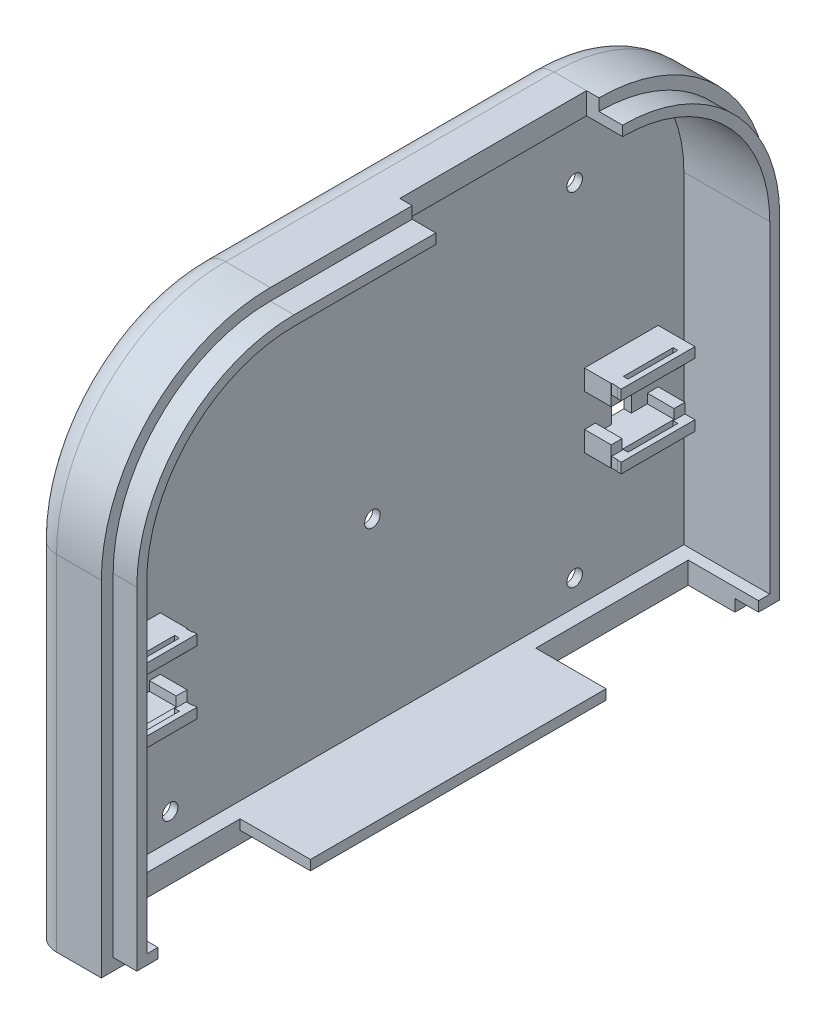
SolidWorks part; units mm, degrees
ref_plane "Front Plane" through (0, 0, 0) normal (0, 0, 1) x (1, 0, 0)
ref_plane "Top Plane" through (0, 0, 0) normal (0, 1, 0) x (1, 0, 0)
ref_plane "Right Plane" through (0, 0, 0) normal (1, 0, 0) x (0, 0, -1)
sketch "Sketch1" plane through (0, 0, 0) normal (1, 0, 0) x (0, 0, -1)
  line L0 (-52.8, 94.65) -> (52.8, 94.65)
  line L1 (-107.1, 40.35) -> (-107.1, -40.35)
  line L2 (-70, -70.35) -> (70, -70.35)
  line L3 (107.1, 40.35) -> (107.1, -40.35)
  line L4 (107.1, 0) -> (-107.1, 0) construction
  line L5 (0, 94.65) -> (0, -70.35) construction
  line L11 (107.1, -40.35) -> (107.1, -70.35)
  line L12 (107.1, -70.35) -> (70, -70.35)
  line L13 (-83.2, -1.7) -> (-76.8, -1.7)
  line L14 (-83.2, -1.7) -> (-83.2, -18.3)
  line L15 (-83.2, -18.3) -> (-76.8, -18.3)
  line L16 (-76.8, -1.7) -> (-76.8, -18.3)
  line L17 (-83.2, -1.7) -> (-76.8, -18.3) construction
  line L18 (-83.2, -18.3) -> (-76.8, -1.7) construction
  line L19 (76.8, -1.7) -> (83.2, -1.7)
  line L20 (76.8, -1.7) -> (76.8, -18.3)
  line L21 (76.8, -18.3) -> (83.2, -18.3)
  line L22 (83.2, -1.7) -> (83.2, -18.3)
  line L23 (76.8, -1.7) -> (83.2, -18.3) construction
  line L24 (76.8, -18.3) -> (83.2, -1.7) construction
  line L25 (80, -10) -> (-80, -10) construction
  line L27 (-107.1, -40.35) -> (-107.1, -70.35)
  line L28 (-107.1, -70.35) -> (-70, -70.35)
  arc A0 (52.8, 94.65) -> (107.1, 40.35) centre (52.8, 40.35) cw
  arc A1 (-52.8, 94.65) -> (-107.1, 40.35) centre (-52.8, 40.35) ccw
  point P16 (0, 0)
  point P17 (-80, -10)
  point P19 (80, 5)
  point P20 (0, -11.7555)
  point P32 (80, -10)
  point P39 (-80, -10)
  point P40 (0, -10)
  dimension "D4" = 54.3
  dimension "D2" = 165
  dimension "D3" = 214.2
  dimension "D5" = 140
  dimension "D6" = 30
  dimension "D7" = 160
  dimension "D8" = 6.4
  dimension "D9" = 16.6
  dimension "D10" = 6.4
  dimension "D11" = 16.6
  dimension "D12" = 10
extrude "Boss-Extrude1" add sketch "Sketch1" along normal blind 2.4 contours L2 L3 A0 L0 A1 L1 L19 L22 L21 L20 L13 L16 L15 L14 region at (0, 9.6593, 0)
sketch "Sketch9" plane through (2.4, 0, 0) normal (1, 0, 0) x (0, 0, -1)
  line L17 (52.8, 94.65) -> (-52.8, 94.65)
  line L31 (52.8, 94.65) -> (-52.8, 94.65)
  line L32 (-107.1, 40.35) -> (-107.1, -70.35)
  line L33 (-107.1, 40.35) -> (-107.1, -70.35)
  line L34 (-107.1, -70.35) -> (107.1, -70.35)
  line L39 (107.1, -70.35) -> (107.1, 40.35)
  line L43 (107.1, -70.35) -> (107.1, 40.35)
  line L45 (-107.1, -70.35) -> (107.1, -70.35)
  arc A15 (-52.8, 94.65) -> (-107.1, 40.35) centre (-52.8, 40.35) ccw
  arc A16 (-52.8, 94.65) -> (-107.1, 40.35) centre (-52.8, 40.35) ccw
  arc A17 (107.1, 40.35) -> (52.8, 94.65) centre (52.8, 40.35) ccw
  arc A18 (107.1, 40.35) -> (52.8, 94.65) centre (52.8, 40.35) ccw
  dimension "D1" = 0
sketch "Sketch10" plane through (2.4, 0, 0) normal (1, 0, 0) x (0, 0, -1)
  line L0 (65, -55.05) -> (0, -55.05) construction
  line L1 (-65, -55.05) -> (65, -55.05) construction
  line L2 (-65, -55.05) -> (-65, 54.95) construction
  line L3 (-65, 54.95) -> (65, 54.95) construction
  line L4 (65, -55.05) -> (65, 54.95) construction
  line L5 (-65, -55.05) -> (65, 54.95) construction
  line L6 (-65, 54.95) -> (65, -55.05) construction
  line L7 (0, -55.05) -> (-65, -55.05) construction
  line L8 (-107.1, -70.35) -> (107.1, -70.35) construction
  line L9 (0, -0.05) -> (0, 0) construction
  line L10 (0, -0.05) -> (0, -6.1) construction
  circle A4 centre (65, 54.95) radius 2.5
  circle A5 centre (65, -55.05) radius 2.5
  circle A6 centre (-65, -55.05) radius 2.5
  circle A7 centre (-65, 54.95) radius 2.5
  circle A11 centre (0, -6.1) radius 2.5
  point P0 (0, -0.05)
  point P11 (0, -55.05)
  point P12 (32.5, -55.05)
  point P14 (-32.5, -55.05)
  dimension "D3" = 5
  dimension "D4" = 15.3
  dimension "D1" = 130
  dimension "D2" = 110
  dimension "D5" = 6.05
extrude "Cut-Extrude1" cut sketch "Sketch10" against normal blind 100 and the other way blind 1000
sketch "Sketch12" plane through (2.4, 0, 0) normal (1, 0, 0) x (0, 0, -1)
  line L5 (-88.35, -18.3) -> (-88.35, -15.3)
  line L6 (-88.35, -18.3) -> (-88.35, -1.7) construction
  line L22 (71.65, -18.3) -> (71.65, -15.3)
  line L23 (71.65, -18.3) -> (71.65, -1.7) construction
  line L24 (71.65, -18.3) -> (88.35, -18.3) construction
  line L25 (88.35, -18.3) -> (88.35, -1.7) construction
  line L26 (71.65, -1.7) -> (88.35, -1.7) construction
  line L27 (71.65, -18.3) -> (88.35, -1.7) construction
  line L28 (88.35, -18.3) -> (71.65, -1.7) construction
  line L29 (71.65, -1.7) -> (71.65, -4.7)
  line L30 (88.35, -18.3) -> (88.35, -15.3)
  line L31 (88.35, -1.7) -> (88.35, -4.7)
  line L32 (71.65, -1.7) -> (88.35, -1.7)
  line L33 (88.35, -18.3) -> (71.65, -18.3)
  line L34 (88.35, -15.3) -> (91.85, -15.3)
  line L35 (71.65, -15.3) -> (68.15, -15.3)
  line L36 (68.15, -15.3) -> (68.15, -21.8)
  line L37 (68.15, -21.8) -> (91.85, -21.8)
  line L38 (91.85, -21.8) -> (91.85, -15.3)
  line L39 (71.65, -4.7) -> (68.15, -4.7)
  line L40 (68.15, -4.7) -> (68.15, 1.8)
  line L41 (68.15, 1.8) -> (91.85, 1.8)
  line L42 (91.85, 1.8) -> (91.85, -4.7)
  line L43 (91.85, -4.7) -> (88.35, -4.7)
  line L44 (83.2, -18.3) -> (76.8, -1.7) construction
  line L45 (83.2, -1.7) -> (76.8, -18.3) construction
  line L46 (-88.35, -18.3) -> (-71.65, -18.3) construction
  line L47 (-71.65, -18.3) -> (-71.65, -1.7) construction
  line L48 (-88.35, -1.7) -> (-71.65, -1.7) construction
  line L49 (-88.35, -18.3) -> (-71.65, -1.7) construction
  line L50 (-71.65, -18.3) -> (-88.35, -1.7) construction
  line L51 (-88.35, -1.7) -> (-88.35, -4.7)
  line L52 (-71.65, -18.3) -> (-71.65, -15.3)
  line L53 (-71.65, -1.7) -> (-71.65, -4.7)
  line L54 (-88.35, -1.7) -> (-71.65, -1.7)
  line L55 (-71.65, -18.3) -> (-88.35, -18.3)
  line L56 (-71.65, -15.3) -> (-68.15, -15.3)
  line L57 (-88.35, -15.3) -> (-91.85, -15.3)
  line L58 (-91.85, -15.3) -> (-91.85, -21.8)
  line L59 (-91.85, -21.8) -> (-68.15, -21.8)
  line L60 (-68.15, -21.8) -> (-68.15, -15.3)
  line L61 (-88.35, -4.7) -> (-91.85, -4.7)
  line L62 (-91.85, -4.7) -> (-91.85, 1.8)
  line L63 (-91.85, 1.8) -> (-68.15, 1.8)
  line L64 (-68.15, 1.8) -> (-68.15, -4.7)
  line L65 (-68.15, -4.7) -> (-71.65, -4.7)
  line L66 (-76.8, -18.3) -> (-83.2, -1.7) construction
  line L67 (-83.2, -18.3) -> (-76.8, -1.7) construction
  point P3 (-0.1438, 64.1533)
  point P4 (-80, -10)
  point P19 (80, -10)
  point P21 (-80, -10)
  point P30 (380.6447, 32.9453)
  point P31 (130.7088, -20.4974)
  point P32 (80, -10)
  point P49 (169.9078, -49.5925)
  dimension "D3" = 16.7
  dimension "D4" = 16.6
  dimension "D5" = 10.6
  dimension "D6" = 3.5
  dimension "D7" = 3.5
  dimension "D8" = 3.5
  dimension "D9" = 3.5
  dimension "D10" = 4.9497
  dimension "D11" = 16.7
  dimension "D12" = 16.6
  dimension "D13" = 10.6
  dimension "D14" = 3.5
  dimension "D15" = 3.5
  dimension "D16" = 3.5
  dimension "D17" = 3.5
  dimension "D18" = 4.9497
  dimension "D19" = 4.9497
  dimension "D20" = 7.3824
  dimension "D21" = 23.5468
  dimension "D22" = 24.088
  dimension "D23" = 4.9497
  dimension "D24" = 7.3824
  dimension "D25" = 23.5468
  dimension "D26" = 24.088
extrude "Boss-Extrude2" add sketch "Sketch12" along normal blind 8.6
sketch "Sketch14" plane through (11, 0, 0) normal (1, 0, 0) x (0, 0, -1)
  line L0 (-91.85, 1.8) -> (-91.85, -4.7) construction
  line L1 (-91.85, 1.8) -> (-68.15, 1.8)
  line L2 (-91.85, 1.8) -> (-91.85, -1.45)
  line L3 (-91.85, -1.45) -> (-68.15, -1.45)
  line L4 (-68.15, 1.8) -> (-68.15, -1.45)
  line L5 (-68.15, 1.8) -> (-91.85, 1.8) construction
  line L6 (-68.15, -4.7) -> (-68.15, 1.8) construction
  line L7 (-68.15, -21.8) -> (-68.15, -15.3) construction
  line L8 (-91.85, -21.8) -> (-68.15, -21.8)
  line L9 (-91.85, -21.8) -> (-91.85, -18.55)
  line L10 (-91.85, -18.55) -> (-68.15, -18.55)
  line L11 (-68.15, -21.8) -> (-68.15, -18.55)
  line L12 (91.85, -21.8) -> (91.85, -15.3) construction
  line L13 (68.15, -21.8) -> (91.85, -21.8)
  line L14 (68.15, -21.8) -> (68.15, -18.55)
  line L15 (68.15, -18.55) -> (91.85, -18.55)
  line L16 (91.85, -21.8) -> (91.85, -18.55)
  line L17 (91.85, -4.7) -> (91.85, 1.8) construction
  line L18 (68.15, 1.8) -> (91.85, 1.8)
  line L19 (68.15, 1.8) -> (68.15, -1.45)
  line L20 (68.15, -1.45) -> (91.85, -1.45)
  line L21 (91.85, 1.8) -> (91.85, -1.45)
extrude "Boss-Extrude3" add sketch "Sketch14" along normal blind 3.2
sketch "Sketch16" plane through (0, -1.45, 0) normal (0, -1, 0) x (1, 0, 0)
  line L0 (11, 91.85) -> (11, 68.15) construction
  line L1 (11, 68.3952) -> (12.9651, 68.3952)
  line L2 (11, 68.3952) -> (11, 51.6632)
  line L3 (11, 51.6632) -> (12.9651, 51.6632)
  line L4 (12.9651, 68.3952) -> (12.9651, 51.6632)
  line L5 (11, -68.15) -> (11, -91.85) construction
  line L6 (11, -51.6659) -> (12.9651, -51.6659)
  line L7 (11, -51.6659) -> (11, -68.2634)
  line L8 (11, -68.2634) -> (12.9651, -68.2634)
  line L9 (12.9651, -51.6659) -> (12.9651, -68.2634)
extrude "Cut-Extrude2" cut sketch "Sketch16" against normal blind 100 and the other way blind 100
sketch "Sketch17" plane through (0, 0, 0) normal (1, 0, 0) x (0, 0, -1)
  line L0 (-103.9, 40.35) -> (-103.9, -67.15) construction
  line L1 (-103.9, -67.15) -> (103.9, -67.15) construction
  line L2 (103.9, -67.15) -> (103.9, 40.35) construction
  line L3 (52.8, 91.45) -> (-52.8, 91.45) construction
  line L4 (52.8, 94.65) -> (-52.8, 94.65)
  line L5 (-107.1, 40.35) -> (-107.1, -70.35)
  line L6 (-107.1, -70.35) -> (107.1, -70.35)
  line L7 (107.1, -70.35) -> (107.1, 40.35)
  line L8 (52.8, 94.65) -> (-52.8, 94.65) construction
  line L9 (-107.1, 40.35) -> (-107.1, -70.35) construction
  line L11 (107.1, -70.35) -> (107.1, 40.35) construction
  line L16 (100.1, -63.35) -> (100.1, 40.35)
  line L17 (52.8, 87.65) -> (-52.8, 87.65)
  line L18 (-100.1, 40.35) -> (-100.1, -63.35)
  line L19 (-100.1, -63.35) -> (100.1, -63.35)
  line L24 (52.8, 90.85) -> (-52.8, 90.85)
  line L25 (-103.3, 40.35) -> (-103.3, -66.55)
  line L27 (103.3, -66.55) -> (103.3, 40.35)
  line L28 (-107.1, -70.35) -> (107.1, -70.35) construction
  line L29 (-103.3, -66.55) -> (103.3, -66.55) construction
  line L31 (-103.3, -66.55) -> (103.3, -66.55)
  arc A0 (103.9, 40.35) -> (52.8, 91.45) centre (52.8, 40.35) ccw construction
  arc A1 (-52.8, 91.45) -> (-103.9, 40.35) centre (-52.8, 40.35) ccw construction
  arc A2 (-52.8, 94.65) -> (-107.1, 40.35) centre (-52.8, 40.35) ccw
  arc A3 (107.1, 40.35) -> (52.8, 94.65) centre (52.8, 40.35) ccw
  arc A4 (-52.8, 94.65) -> (-107.1, 40.35) centre (-52.8, 40.35) ccw construction
  arc A5 (107.1, 40.35) -> (52.8, 94.65) centre (52.8, 40.35) ccw construction
  arc A8 (100.1, 40.35) -> (52.8, 87.65) centre (52.8, 40.35) ccw
  arc A9 (-52.8, 87.65) -> (-100.1, 40.35) centre (-52.8, 40.35) ccw
  arc A12 (-52.8, 90.85) -> (-103.3, 40.35) centre (-52.8, 40.35) ccw
  arc A13 (103.3, 40.35) -> (52.8, 90.85) centre (52.8, 40.35) ccw
  dimension "D4" = 157.4
  dimension "D5" = 206.6
  dimension "D7" = 207.8
  dimension "D8" = 214.2
  dimension "D9" = 3.2
  dimension "D2" = 3.2
  dimension "D10" = 3.2
  dimension "D11" = 3.2
  dimension "D1" = 0
  dimension "D3" = 3.2
  dimension "D6" = 0.6
extrude "Boss-Extrude4" add sketch "Sketch17" along normal blind 30
sketch "Sketch21" plane through (2.4, 0, 0) normal (1, 0, 0) x (0, 0, -1)
  line L4 (-107.1, -70.35) -> (107.1, -70.35)
  line L6 (-107.1, -70.35) -> (107.1, -70.35)
  line L8 (52.8, 94.65) -> (-52.8, 94.65)
  line L9 (-107.1, 40.35) -> (-107.1, -70.35)
  line L11 (107.1, -70.35) -> (107.1, 40.35)
  line L12 (52.8, 94.65) -> (-52.8, 94.65)
  line L13 (-107.1, 40.35) -> (-107.1, -70.35)
  line L15 (107.1, -70.35) -> (107.1, 40.35)
  arc A4 (-52.8, 94.65) -> (-107.1, 40.35) centre (-52.8, 40.35) ccw
  arc A5 (107.1, 40.35) -> (52.8, 94.65) centre (52.8, 40.35) ccw
  arc A6 (-52.8, 94.65) -> (-107.1, 40.35) centre (-52.8, 40.35) ccw
  arc A7 (107.1, 40.35) -> (52.8, 94.65) centre (52.8, 40.35) ccw
  dimension "D1" = 0
sketch "Sketch22" plane through (2.4, 0, 0) normal (1, 0, 0) x (0, 0, -1)
  line L0 (-107.1, -70.35) -> (107.1, -70.35) construction
  line L1 (-107.1, -70.35) -> (107.1, -70.35)
  line L21 (52.8, 94.65) -> (-52.8, 94.65)
  line L22 (107.1, -70.35) -> (107.1, 40.35)
  line L24 (-107.1, 40.35) -> (-107.1, -70.35)
  line L25 (52.8, 94.65) -> (-52.8, 94.65)
  line L26 (107.1, -70.35) -> (107.1, 40.35)
  line L28 (-107.1, 40.35) -> (-107.1, -70.35)
  line L44 (-103.3, -66.55) -> (103.3, -66.55)
  line L45 (103.3, -66.55) -> (103.3, 40.35)
  line L46 (52.8, 90.85) -> (-52.8, 90.85)
  line L47 (-103.3, 40.35) -> (-103.3, -66.55)
  line L48 (-103.3, -66.55) -> (103.3, -66.55)
  line L49 (103.3, -66.55) -> (103.3, 40.35)
  line L50 (52.8, 90.85) -> (-52.8, 90.85)
  line L51 (-103.3, 40.35) -> (-103.3, -66.55)
  arc A6 (-52.8, 94.65) -> (-107.1, 40.35) centre (-52.8, 40.35) ccw
  arc A7 (107.1, 40.35) -> (52.8, 94.65) centre (52.8, 40.35) ccw
  arc A8 (-52.8, 94.65) -> (-107.1, 40.35) centre (-52.8, 40.35) ccw
  arc A9 (107.1, 40.35) -> (52.8, 94.65) centre (52.8, 40.35) ccw
  arc A20 (103.3, 40.35) -> (52.8, 90.85) centre (52.8, 40.35) ccw
  arc A21 (-52.8, 90.85) -> (-103.3, 40.35) centre (-52.8, 40.35) ccw
  arc A22 (103.3, 40.35) -> (52.8, 90.85) centre (52.8, 40.35) ccw
  arc A23 (-52.8, 90.85) -> (-103.3, 40.35) centre (-52.8, 40.35) ccw
  dimension "D1" = 0
  dimension "D2" = 0
extrude "Boss-Extrude7" add sketch "Sketch22" along normal blind 20
sketch "Sketch23" plane through (0, -70.35, 0) normal (0, -1, 0) x (1, 0, 0)
  line L0 (0, 99.1) -> (0, 107.1)
  line L1 (0, 107.1) -> (8, 107.1)
  line L2 (8, -107.1) -> (0, -107.1)
  line L3 (0, -107.1) -> (0, -99.1)
  line L8 (0, 107.1) -> (0, -107.1)
  line L9 (0, -107.1) -> (22.4, -107.1)
  line L10 (22.4, -107.1) -> (22.4, 107.1)
  line L11 (22.4, 107.1) -> (0, 107.1)
  line L12 (0, 99.1) -> (0, -99.1) construction
  line L13 (8, -107.1) -> (22.4, -107.1) construction
  line L15 (22.4, 107.1) -> (8, 107.1) construction
  arc A0 (0, 99.1) -> (8, 107.1) centre (8, 99.1) cw
  arc A1 (0, -99.1) -> (8, -107.1) centre (8, -99.1) ccw
  dimension "D2" = 8
  dimension "D1" = 0
extrude "Cut-Extrude4" cut sketch "Sketch23" against normal through all
fillet "Fillet4" radius 8 5 edges at (0, 87.7258, 79.3335) (0, 94.65, 0) (0, 87.7258, -79.3335) (1.5353, 58.957, 103.8124) (1.5353, 58.957, -103.8124)
sketch "Sketch26" plane through (22.4, 0, 0) normal (1, 0, 0) x (0, 0, -1)
  line L1 (-47.5, -63.3365) -> (47.5, -63.3365)
  line L2 (47.5, -63.3365) -> (47.5, -66.55)
  line L6 (47.5, -66.55) -> (-47.5, -66.55)
  line L7 (-47.5, -66.55) -> (-47.5, -63.3365)
  line L8 (-103.3, -66.55) -> (103.3, -66.55) construction
  line L9 (-96.5, -74.5369) -> (96.5, -74.5369)
  line L10 (-96.5, -74.5369) -> (-96.5, -58.5631)
  line L11 (-96.5, -58.5631) -> (96.5, -58.5631)
  line L12 (96.5, -74.5369) -> (96.5, -58.5631)
  line L13 (-96.5, -74.5369) -> (96.5, -58.5631) construction
  line L14 (-96.5, -58.5631) -> (96.5, -74.5369) construction
  line L15 (107.1, -70.35) -> (107.1, 40.35) construction
  point P0 (0, -66.55)
  point P9 (0, -63.3365)
  point P13 (0, -63.3365)
  point P16 (0, -63.3365)
  dimension "D1" = 10.6
  dimension "D2" = 15.9739
  dimension "D3" = 95
  dimension "D4" = 3.2135
extrude "Cut-Extrude7" cut sketch "Sketch26" against normal blind 15 and the other way blind 20
sketch "Sketch28" plane through (0, 94.65, 0) normal (0, 1, 0) x (1, 0, 0)
  line L0 (22.4, 52.8) -> (18.4, 52.8)
  line L1 (22.4, 52.8) -> (8, 52.8) construction
  line L2 (18.4, 52.8) -> (18.4, -7.2)
  line L3 (18.4, -7.2) -> (53.1003, -7.2)
  line L4 (53.1003, -7.2) -> (53.1003, 52.8)
  line L5 (53.1003, 52.8) -> (22.4, 52.8)
  dimension "D1" = 4
  dimension "D2" = 60
extrude "Cut-Extrude8" cut sketch "Sketch28" against normal blind 10
sketch "Sketch29" plane through (0, -1.45, 0) normal (0, -1, 0) x (1, 0, 0)
  line L5 (11, 91.85) -> (11, 68.3952) construction
  line L7 (11, 88.1226) -> (11, 72.1226)
  line L8 (11, 72.1226) -> (12.5, 72.1226)
  line L9 (12.5, 72.1226) -> (12.5, 88.1226)
  line L10 (12.5, 88.1226) -> (11, 88.1226)
  line L12 (11, -68.2634) -> (11, -91.85) construction
  line L13 (11, -72.0567) -> (11, -88.0567)
  line L14 (11, -88.0567) -> (12.5, -88.0567)
  line L15 (12.5, -88.0567) -> (12.5, -72.0567)
  line L16 (12.5, -72.0567) -> (11, -72.0567)
  point P0 (11, 80.1226)
  point P1 (11, -80.0567)
  point P6 (11, 80.1226)
  point P9 (11, -80.0567)
  point P14 (11, -80.0567)
  dimension "D1" = 16
  dimension "D2" = 1.5
  dimension "D3" = 16
  dimension "D4" = 1.5
extrude "Cut-Extrude9" cut sketch "Sketch29" against normal blind 30 and the other way blind 1000
